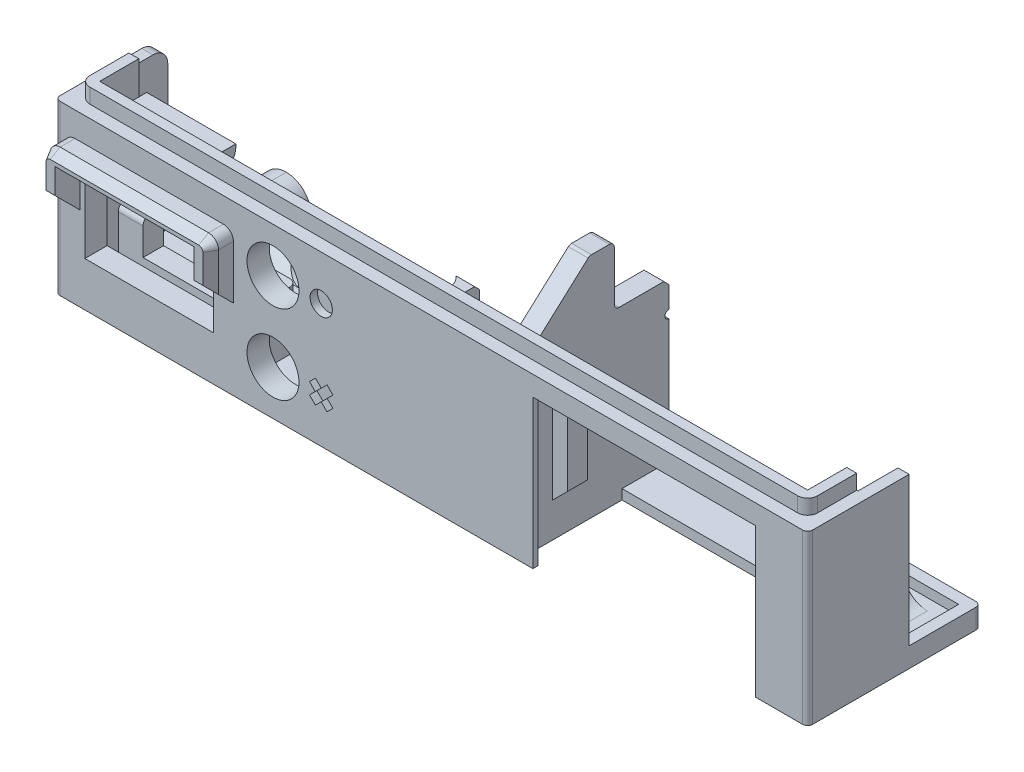
SolidWorks part; units mm, degrees
ref_plane "Plano frontal" through (0, 0, 0) normal (0, 0, 1) x (1, 0, 0)
ref_plane "Plano superior" through (0, 0, 0) normal (0, 1, 0) x (1, 0, 0)
ref_plane "Plano direito" through (0, 0, 0) normal (1, 0, 0) x (0, 0, -1)
sketch "Esboço1" plane through (0, 0, 0) normal (0, 1, 0) x (1, 0, 0)
  line L1 (0, 0) -> (152, 0)
  line L2 (0, 0) -> (0, 35)
  line L3 (0, 35) -> (152, 35)
  line L4 (152, 0) -> (152, 35)
extrude "Ressalto-extrusão1" add sketch "Esboço1" along normal blind 2
sketch "Esboço3" plane through (0, 2, 0) normal (0, 1, 0) x (1, 0, 0)
  line L0 (4.5, 12.4) -> (4.5, 4.5)
  line L1 (4.5, 4.5) -> (89.5, 4.5)
  line L2 (147.5, 4.5) -> (147.5, 12.4)
  line L3 (149.75, 32.75) -> (2.25, 32.75)
  line L8 (0, 35) -> (0, 0)
  line L9 (0, 0) -> (152, 0)
  line L10 (152, 0) -> (152, 35)
  line L11 (152, 35) -> (0, 35)
  line L12 (0, 35) -> (0, 0)
  line L13 (0, 0) -> (152, 0)
  line L14 (152, 0) -> (152, 35)
  line L15 (152, 35) -> (0, 35)
  line L16 (147.5, 12.4) -> (149.75, 12.4)
  line L17 (149.75, 12.4) -> (149.75, 32.75)
  line L18 (4.5, 12.4) -> (2.25, 12.4)
  line L19 (2.25, 12.4) -> (2.25, 32.75)
  line L20 (93.5, 4.5) -> (93.5, 30.45)
  line L21 (93.5, 30.45) -> (89.5, 30.45)
  line L22 (89.5, 30.45) -> (89.5, 4.5)
  line L24 (93.5, 4.5) -> (147.5, 4.5)
  dimension "D3" = 12.4
  dimension "D4" = 2.25
  dimension "D2" = 4.5
  dimension "D5" = 4.5
  dimension "D6" = 4.5
  dimension "D7" = 2.25
  dimension "D8" = 12.4
  dimension "D9" = 2.25
  dimension "D10" = 58.5
  dimension "D11" = 4
  dimension "D12" = 2.3
  dimension "D1" = 0
extrude "Ressalto-extrusão2" add sketch "Esboço3" along normal blind 32
sketch "Esboço5" plane through (0, 34, 0) normal (0, 1, 0) x (1, 0, 0)
  line L0 (152, 0) -> (152, 35) construction
  line L1 (0, 35) -> (152, 35)
  line L2 (0, 35) -> (0, 20.5)
  line L3 (0, 20.5) -> (2.25, 20.5)
  line L4 (152, 35) -> (152, 20.5)
  line L5 (149.75, 20.5) -> (149.75, 32.75)
  line L6 (149.75, 12.4) -> (149.75, 32.75) construction
  line L7 (149.75, 32.75) -> (2.25, 32.75)
  line L8 (2.25, 32.75) -> (2.25, 20.5)
  line L9 (2.25, 32.75) -> (2.25, 12.4) construction
  line L10 (149.75, 20.5) -> (152, 20.5)
  dimension "D1" = 14.5
extrude "Corte-extrusão1" cut sketch "Esboço5" against normal blind 30
fillet "Filete2" radius 3 1 edges at (1.125, 34, -20.5)
fillet "Filete3" radius 1 4 edges at (152, 2, -35) (0, 2, -35) (152, 17, 0) (0, 17, 0)
sketch "Esboço7" plane through (0, 0, 0) normal (0, 0, 1) x (1, 0, 0)
  line L0 (1, 34) -> (151, 34) construction
  line L1 (6, 25) -> (32, 25)
  line L2 (6, 25) -> (6, 9)
  line L3 (6, 9) -> (32, 9)
  line L4 (32, 25) -> (32, 9)
  line L5 (4.5, 34) -> (4.5, 2) construction
  line L6 (6, 25) -> (44, 25) construction
  line L7 (44, 25) -> (44, 9) construction
  circle A0 centre (44, 25) radius 5.25
  circle A1 centre (44, 9) radius 5.25
  point P6 (20, 9)
  point P12 (36.4031, 24.9)
  dimension "D5" = 10.5
  dimension "D6" = 10.5
  dimension "D7" = 1.5
  dimension "D1" = 16
  dimension "D2" = 26
  dimension "D3" = 9
  dimension "D4" = 12
  dimension "D10" = 16
extrude "Corte-extrusão2" cut sketch "Esboço7" against normal up to surface (4.5 mm away) up to face at (47, 18, -4.5)
sketch "Esboço8" plane through (0, 0, 0) normal (0, 0, 1) x (1, 0, 0)
  line L0 (49.25, 9) -> (53.75, 9) construction
  line L1 (52.5833, 11.3688) -> (53.75, 10.2021)
  line L2 (51.25, 6.5) -> (56.25, 6.5) construction
  line L3 (51.25, 6.5) -> (51.25, 11.5) construction
  line L4 (51.25, 11.5) -> (56.25, 11.5) construction
  line L5 (56.25, 6.5) -> (56.25, 11.5) construction
  line L6 (51.25, 6.5) -> (56.25, 11.5) construction
  line L7 (51.25, 11.5) -> (56.25, 6.5) construction
  line L8 (52.5833, 11.3688) -> (51.3812, 10.1667)
  line L9 (56.1188, 7.8333) -> (54.9167, 6.6312)
  line L10 (51.3812, 10.1667) -> (52.5479, 9)
  line L11 (52.5833, 11.3688) -> (54.9167, 6.6312) construction
  line L12 (56.1188, 7.8333) -> (51.3812, 10.1667) construction
  line L13 (56.1188, 10.1667) -> (54.9521, 9)
  line L14 (56.1188, 10.1667) -> (54.9167, 11.3688)
  line L15 (52.5833, 6.6312) -> (51.3812, 7.8333)
  line L16 (54.9167, 11.3688) -> (53.75, 10.2021)
  line L17 (56.1188, 10.1667) -> (51.3812, 7.8333) construction
  line L18 (52.5833, 6.6312) -> (54.9167, 11.3688) construction
  line L19 (53.75, 7.7979) -> (54.9167, 6.6312)
  line L20 (53.75, 7.7979) -> (52.5833, 6.6312)
  line L21 (54.9521, 9) -> (56.1188, 7.8333)
  line L22 (52.5479, 9) -> (51.3812, 7.8333)
  line L23 (49.25, 25) -> (53.75, 25) construction
  circle A0 centre (53.75, 9) radius 2.5 construction
  circle A1 centre (44, 9) radius 5.25 construction
  circle A3 centre (53.75, 25) radius 2.25
  circle A4 centre (44, 25) radius 5.25 construction
  point P7 (49.25, 9)
  point P15 (38.75, 25)
  point P24 (38.75, 25)
  point P25 (49.25, 25)
  dimension "D1" = 5
  dimension "D3" = 4.5
  dimension "D2" = 4.5
  dimension "D4" = 4.5
extrude "Corte-extrusão3" cut sketch "Esboço8" against normal blind 1.5
sketch "Esboço10" plane through (0, 0, 0) normal (0, -1, 0) x (1, 0, 0)
  line L0 (1, 0) -> (151, 0) construction
  line L1 (144.5, 0) -> (93.5, 0)
  line L2 (144.5, 0) -> (144.5, -21)
  line L3 (144.5, -21) -> (93.5, -21)
  line L4 (93.5, 0) -> (93.5, -21)
  line L5 (151, -35) -> (1, -35) construction
  line L6 (152, -1) -> (152, -34) construction
  point P0 (144.5, 0)
  point P3 (93.5, 0)
  dimension "D1" = 14
  dimension "D2" = 7.5
  dimension "D3" = 51
extrude "Corte-extrusão5" cut sketch "Esboço10" along direction (0, -1, 0) on the side against the normal blind 30
sketch "Esboço12" plane through (0, 0, 0) normal (0, -1, 0) x (1, 0, 0)
  line L0 (93.5, 0) -> (93.5, -21) construction
  line L1 (74.5, -8.25) -> (88.5, -8.25)
  line L2 (74.5, -8.25) -> (74.5, -27.75)
  line L3 (74.5, -27.75) -> (88.5, -27.75)
  line L4 (88.5, -8.25) -> (88.5, -27.75)
  line L6 (55.75, -12.0976) -> (68.25, -18.4024) construction
  line L8 (55.75, -18.4024) -> (55.75, -12.0976)
  line L10 (68.25, -18.4024) -> (68.25, -12.0976)
  line L11 (68.25, -12.0976) -> (55.75, -18.4024) construction
  line L12 (62, -15.25) -> (74.5, -15.25) construction
  line L14 (74.5, -8.25) -> (62, -8.25) construction
  line L19 (1, 0) -> (93.5, 0) construction
  line L32 (62, -15.25) -> (62, -32) construction
  line L33 (151, -35) -> (1, -35) construction
  line L35 (58, -29) -> (66, -29)
  line L36 (58, -29) -> (58, -35)
  line L37 (58, -35) -> (66, -35)
  line L38 (66, -29) -> (66, -35)
  line L39 (58, -29) -> (66, -35) construction
  line L40 (58, -35) -> (66, -29) construction
  arc A0 (55.75, -18.4024) -> (68.25, -18.4024) centre (62, -15.25) ccw
  arc A1 (68.25, -12.0976) -> (55.75, -12.0976) centre (62, -15.25) ccw
  circle A2 centre (62, -15.25) radius 7 construction
  dimension "D4" = 7
  dimension "D6" = 12.5
  dimension "D1" = 14
  dimension "D2" = 19.5
  dimension "D3" = 5
  dimension "D5" = 12.5
  dimension "D7" = 8.25
  dimension "D11" = 6
  dimension "D17" = 8
extrude "Corte-extrusão7" cut sketch "Esboço12" against normal blind 16
sketch "Esboço15" plane through (0, 2, 0) normal (0, 1, 0) x (1, 0, 0)
  line L0 (68.6192, 22.35) -> (67.1192, 23.85)
  line L1 (68.8233, 24.75) -> (67.1192, 24.75)
  line L2 (68.8233, 24.75) -> (68.8233, 30.45)
  line L4 (55.2871, 24.75) -> (55.2871, 30.45)
  line L5 (149.75, 32.75) -> (66, 32.75) construction
  line L6 (89.5, 30.45) -> (93.5, 30.45) construction
  line L7 (51.2871, 30.45) -> (51.2871, 29.65)
  line L8 (52.8871, 22.35) -> (52.8871, 26.45)
  line L9 (71.2233, 22.35) -> (68.6192, 22.35)
  line L10 (71.2233, 22.35) -> (71.2233, 26.45)
  line L11 (56.9912, 24.75) -> (55.2871, 24.75)
  line L12 (55.4912, 22.35) -> (52.8871, 22.35)
  line L14 (67.1192, 24.75) -> (67.1192, 23.85)
  line L16 (56.9912, 24.75) -> (56.9912, 23.85)
  line L17 (68.8233, 24.75) -> (55.2871, 24.75) construction
  line L19 (71.2233, 22.35) -> (52.8871, 22.35) construction
  line L21 (56.9912, 23.85) -> (55.4912, 22.35)
  line L23 (72.8233, 30.45) -> (72.8233, 29.65)
  line L24 (71.2233, 22.35) -> (71.2233, 30.45) construction
  line L26 (68.8233, 30.45) -> (72.8233, 30.45)
  line L27 (52.8871, 22.35) -> (52.8871, 30.45) construction
  line L28 (55.2871, 30.45) -> (51.2871, 30.45)
  arc A0 (71.2233, 26.45) -> (72.8233, 29.65) centre (75.2233, 26.45) cw
  arc A1 (51.2871, 29.65) -> (52.8871, 26.45) centre (48.8871, 26.45) cw
  point P0 (62.0552, 27.75)
  point P13 (62.0552, 23.55)
  point P14 (56.9912, 22.35)
  point P16 (67.1192, 22.35)
  point P23 (67.1192, 24.3)
  dimension "D3" = 1.5
  dimension "D6" = 4
  dimension "D7" = 4
  dimension "D1" = 1.5
  dimension "D2" = 2.4
  dimension "D4" = 1.5
  dimension "D5" = 1.5
  dimension "D8" = 10.4
  dimension "D9" = 13.5363
  dimension "D10" = 10.1279
  dimension "D11" = 0.8
  dimension "D12" = 4.1
  dimension "D13" = 4.1
  dimension "D14" = 0.8
extrude "Ressalto-extrusão4" add sketch "Esboço15" along normal blind 12
fillet "Filete16" radius 1.5 12 edges at (52.4648, 2, -28.2389) (71.6456, 2, -28.2389) (51.2871, 2, -30.05) (52.8871, 2, -24.4) (72.8233, 2, -30.05) (71.2233, 2, -24.4) (67.1192, 2, -24.3) (56.9912, 2, -24.3) (69.9212, 2, -22.35) (67.8692, 2, -23.1) (56.2412, 2, -23.1) (54.1891, 2, -22.35)
chamfer "Chanfro2" distance 1 angle 45 3 edges at (91.5, 34, -30.45) (70.8233, 14, -30.45) (53.2871, 14, -30.45)
sketch "Esboço18" plane through (6, 0, 0) normal (1, 0, 0) x (0, 0, -1)
  line L0 (4.5, 3.8) -> (8.25, 3.8)
  line L1 (12.4, 34) -> (12.4, 2) construction
  line L3 (8.25, 6.8) -> (12.4, 6.8)
  line L7 (8.25, 3.8) -> (8.25, 6.8)
  line L8 (4.5, 34) -> (4.5, 2) construction
  line L9 (12.4, 6.8) -> (12.4, 2)
  line L10 (30.75, 2) -> (4.25, 2) construction
  line L11 (12.4, 2) -> (4.5, 2)
  line L12 (4.5, 2) -> (4.5, 3.8)
  point P14 (12.4, 6.8)
  point P18 (8.25, 6.8)
  dimension "D2" = 1.8
  dimension "D3" = 3.75
  dimension "D1" = 3
extrude "Ressalto-extrusão6" add sketch "Esboço18" along normal blind 29 and the other way blind 1 from surface at -1.5 starting at face at (4.5, 18, -8.45)
sketch "Esboço31" plane through (0, 34, 0) normal (0, 1, 0) x (1, 0, 0)
  line L0 (147.5, 12.4) -> (149.5, 12.4)
  line L1 (147.5, 12.4) -> (149.75, 12.4) construction
  line L2 (149.5, 12.4) -> (149.5, 2.5)
  line L3 (149.5, 2.5) -> (2.5, 2.5)
  line L4 (2.5, 2.5) -> (2.5, 12.4)
  line L5 (2.25, 12.4) -> (4.5, 12.4) construction
  line L6 (2.5, 12.4) -> (4.5, 12.4)
  line L7 (4.5, 12.4) -> (4.5, 4.5)
  line L8 (4.5, 4.5) -> (147.5, 4.5)
  line L9 (147.5, 4.5) -> (147.5, 12.4)
  dimension "D1" = 2
  dimension "D2" = 2
  dimension "D3" = 2
extrude "Ressalto-extrusão13" add sketch "Esboço31" along normal blind 3
ref_plane "Plano1" through (89.5, 2, -4.5) normal (1, 0, 0) x (0, 0, -1)
sketch "Esboço34" plane through (0, 0, 0) normal (0, -1, 0) x (1, 0, 0)
  line L0 (96.5, -1) -> (93.5, -4)
  line L1 (93.5, 0) -> (96.5, 0)
  line L2 (93.5, 0) -> (93.5, -4)
  line L5 (144.5, 0) -> (141.5, 0)
  line L6 (144.5, 0) -> (144.5, -4)
  line L9 (96.5, 0) -> (96.5, -1)
  line L10 (141.5, -1) -> (144.5, -4)
  line L11 (141.5, 0) -> (141.5, -1)
  dimension "D1" = 45
  dimension "D2" = 1
  dimension "D3" = 4
  dimension "D4" = 45
  dimension "D5" = 4
  dimension "D6" = 1
extrude "Ressalto-extrusão14" add sketch "Esboço34" along direction (0, -1, 0) on the side against the normal up to surface (34 mm away)
sketch "Esboço35" plane through (0, 2, 0) normal (0, 1, 0) x (1, 0, 0)
  line L0 (93.5, 30.45) -> (93.5, 21) construction
  line L1 (93.5, 11) -> (96.5, 11)
  line L2 (93.5, 11) -> (93.5, 7)
  line L3 (93.5, 7) -> (96.5, 7)
  line L4 (96.5, 11) -> (96.5, 7)
  line L5 (147.5, 4.5) -> (147.5, 12.4) construction
  line L6 (147.5, 7) -> (141.5, 7)
  line L7 (147.5, 7) -> (147.5, 12.4)
  line L8 (147.5, 12.4) -> (141.5, 12.4)
  line L9 (141.5, 7) -> (141.5, 12.4)
  line L10 (144.5, 21) -> (144.5, 4) construction
  line L11 (147.5, 12.4) -> (149.75, 12.4) construction
  dimension "D1" = 3
  dimension "D2" = 4
  dimension "D3" = 3
  dimension "D4" = 3
  dimension "D5" = 3
extrude "Ressalto-extrusão15" add sketch "Esboço35" along normal blind 15 from offset 8
chamfer "Chanfro3" distance 3 angle 45 1 edges at (93.5, 10, -9)
chamfer "Chanfro4" distance 6 angle 45 1 edges at (147.5, 10, -9.7)
chamfer "Chanfro5" distance 6 angle 45 1 edges at (147.5, 25, -9.7)
chamfer "Chanfro6" distance 3 angle 45 1 edges at (93.5, 25, -9)
sketch "Esboço36" plane through (0, 2, 0) normal (0, 1, 0) x (1, 0, 0)
  line L1 (11.25, 30.45) -> (21.25, 30.45)
  line L2 (11.25, 30.45) -> (11.25, 26.45)
  line L3 (11.25, 26.45) -> (21.25, 26.45)
  line L4 (21.25, 30.45) -> (21.25, 26.45)
  line L5 (130.75, 30.45) -> (140.75, 30.45)
  line L6 (130.75, 30.45) -> (130.75, 26.45)
  line L7 (130.75, 26.45) -> (140.75, 26.45)
  line L8 (140.75, 30.45) -> (140.75, 26.45)
  line L11 (2.25, 32.75) -> (2.25, 12.4) construction
  line L12 (89.5, 30.45) -> (93.5, 30.45) construction
  line L13 (149.75, 12.4) -> (149.75, 32.75) construction
  dimension "D1" = 4
  dimension "D2" = 10
  dimension "D3" = 9
  dimension "D4" = 10
  dimension "D5" = 4
  dimension "D6" = 9
extrude "Ressalto-extrusão16" add sketch "Esboço36" along normal blind 12
fillet "Filete20" radius 5 8 edges at (140.75, 2, -28.45) (140.75, 14, -28.45) (130.75, 14, -28.45) (130.75, 2, -28.45) (21.25, 2, -28.45) (21.25, 14, -28.45) (11.25, 14, -28.45) (11.25, 2, -28.45)
chamfer "Chanfro7" distance 3 angle 45 2 edges at (135.75, 2, -26.45) (16.25, 2, -26.45)
sketch "Esboço37" plane through (0, 0, -26.45) normal (0, 0, 1) x (1, 0, 0)
  line L0 (11.25, 9) -> (11.25, 7) construction
  line L1 (130.75, 9) -> (130.75, 7) construction
  circle A0 centre (16.25, 9) radius 1.25
  circle A1 centre (135.75, 9) radius 1.25
  dimension "D1" = 5
  dimension "D3" = 2.5
  dimension "D4" = 5
  dimension "D2" = 5
  dimension "D5" = 5
extrude "Corte-extrusão8" cut sketch "Esboço37" against normal through all
sketch "Esboço38" plane through (89.5, 0, 0) normal (-1, 0, 0) x (0, 0, 1)
  line L1 (-19.45, 34) -> (-19.45, 46)
  line L2 (-19.45, 46) -> (-14.45, 46)
  line L4 (-4.5, 34) -> (-4.5, 37)
  line L5 (-4.5, 37) -> (-14.45, 46)
  line L6 (-19.45, 34) -> (-4.5, 34)
  line L8 (-4.5, 34) -> (-29.45, 34) construction
  line L9 (-4.5, 30) -> (-4.5, 2) construction
  dimension "D1" = 14.95
  dimension "D2" = 12
extrude "Ressalto-extrusão17" add sketch "Esboço38" against normal up to surface (4 mm away) up to face at (93.5, 17.5, -9)
fillet "Filete21" radius 1 1 edges at (91.5, 34, -19.45)
fillet "Filete22" radius 1 2 edges at (91.5, 46, -14.45) (91.5, 46, -19.45)
fillet "Filete23" radius 2 2 edges at (149.5, 35.5, -2.5) (2.5, 35.5, -2.5)
sketch "Esboço39" plane through (93.5, 0, 0) normal (1, 0, 0) x (0, 0, -1)
  line L0 (30.45, 33) -> (30.45, 2) construction
  line L1 (30.45, 27) -> (30.45, 28.6)
  arc A0 (30.45, 28.6) -> (30.45, 27) centre (30.45, 27.8) ccw
  dimension "D1" = 0.8
  dimension "D2" = 25
extrude "Corte-extrusão9" cut sketch "Esboço39" against normal up to surface (4 mm away) up to face at (89.5, 32.7095, -18.7387)
sketch "Esboço40" plane through (0, 2, 0) normal (0, 1, 0) x (1, 0, 0)
  line L3 (9.5, 12.4) -> (9.5, 8.25)
  line L4 (9.5, 8.25) -> (4.5, 8.25)
  line L10 (19, 4.5) -> (19, 14.5) construction
  line L11 (33.5, 4.5) -> (89.5, 4.5) construction
  line L12 (33.5, 4.5) -> (36.5, 4.5)
  line L13 (33.5, 8.25) -> (33.5, 4.5)
  line L14 (28.5, 8.25) -> (33.5, 8.25)
  line L15 (28.5, 12.4) -> (28.5, 8.25)
  line L16 (36.5, 12.4) -> (28.5, 12.4)
  line L17 (36.5, 4.5) -> (36.5, 12.4)
  line L20 (4.5, 8.25) -> (4.5, 12.4)
  line L21 (9.5, 12.4) -> (4.5, 12.4)
  line L22 (6, 4.5) -> (6, 0) construction
  line L23 (4.5, 12.4) -> (33.5, 12.4) construction
  dimension "D1" = 13
  dimension "D2" = 14.5
  dimension "D4" = 3.75
  dimension "D5" = 5
  dimension "D6" = 3
extrude "Ressalto-extrusão19" add sketch "Esboço40" along normal offset from surface (11.8 mm away) 10 up to face at (19, 3.8, -6.375) offset beyond the face yes
fillet "Filete24" radius 1.5 3 edges at (7, 13.8, -8.25) (31, 13.8, -8.25) (36.5, 7.9, -12.4)
sketch "Esboço42" plane through (0, 0, -4.5) normal (0, 0, -1) x (-1, 0, 0)
  line L0 (-32, 9) -> (-32, 25) construction
  line L1 (-28, 31.8) -> (-10, 31.8)
  line L2 (-28, 31.8) -> (-28, 35.8)
  line L3 (-28, 35.8) -> (-10, 35.8)
  line L4 (-10, 31.8) -> (-10, 35.8)
  line L5 (-6, 25) -> (-6, 9) construction
  line L6 (-4.5, 3.8) -> (-33.5, 3.8) construction
  point P6 (-10, 33.8)
  dimension "D1" = 4
  dimension "D2" = 4
  dimension "D3" = 28
  dimension "D4" = 4
extrude "Ressalto-extrusão20" add sketch "Esboço42" along normal blind 4
fillet "Filete25" radius 3.5 1 edges at (19, 31.8, -8.5)
sketch "Esboço44" plane through (0, 0, 0) normal (0, 0, 1) x (1, 0, 0)
  line L0 (5, 26) -> (33, 26)
  line L1 (33, 26) -> (33, 16.208)
  line L3 (33, 16.208) -> (36, 16.208)
  line L4 (36, 16.208) -> (36, 29)
  line L5 (36, 29) -> (2, 29)
  line L6 (2, 29) -> (2, 17)
  line L7 (2, 17) -> (5, 17)
  line L9 (5, 17) -> (5, 26)
  line L11 (6, 25) -> (6, 9) construction
  line L12 (32, 25) -> (6, 25) construction
  line L13 (32, 9) -> (32, 25) construction
  dimension "D1" = 3
  dimension "D2" = 3
  dimension "D3" = 3
  dimension "D4" = 1
  dimension "D5" = 1
  dimension "D6" = 1
extrude "Ressalto-extrusão21" add sketch "Esboço44" along normal blind 5
chamfer "Chanfro8" distance 5 angle 45 2 edges at (34.5, 16.208, 5) (3.5, 17, 5)
chamfer "Chanfro9" distance 3 angle 20 1 edges at (19, 26, 5)
fillet "Filete26" radius 2 2 edges at (36, 29, 2.5) (2, 29, 2.5)
chamfer "Chanfro10" distance 2 angle 30 5 edges at (36, 24.104, 5) (35.4142, 28.4142, 5) (19, 29, 5) (2.5858, 28.4142, 5) (2, 24.5, 5)
